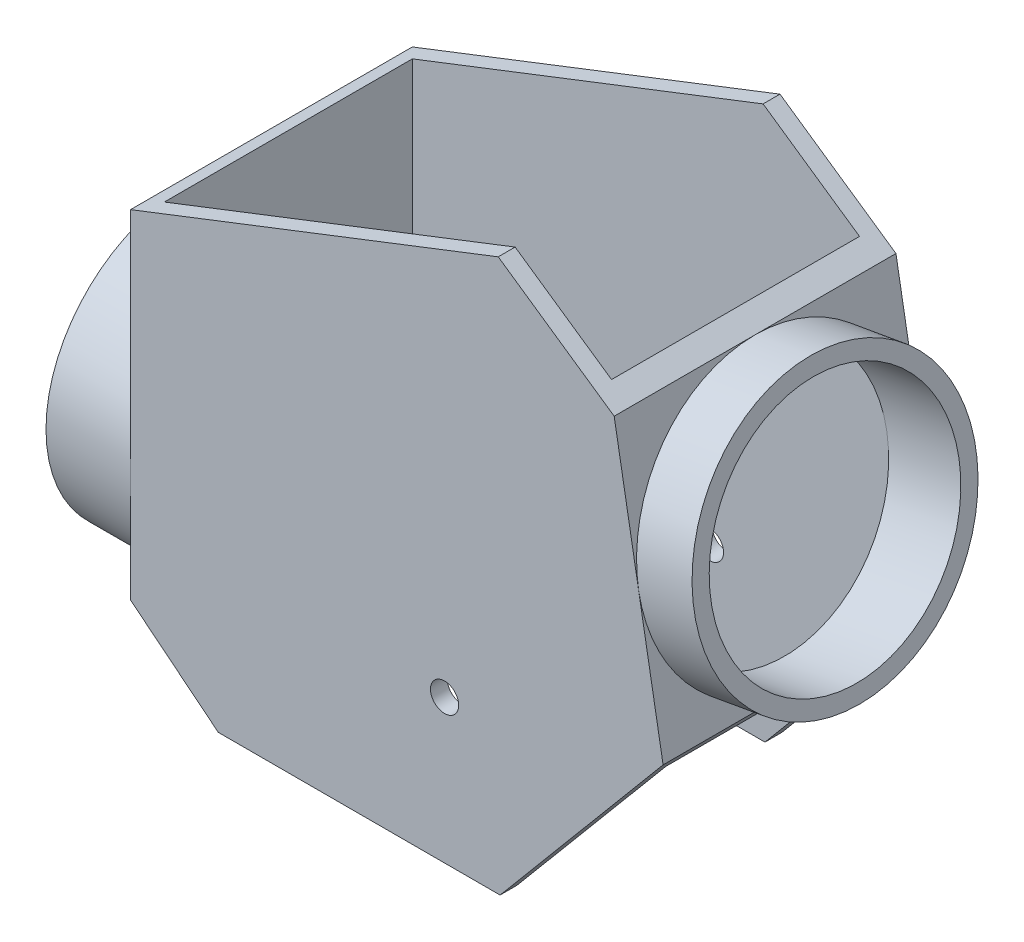
SolidWorks part; units mm, degrees
ref_plane "Plan de face" through (0, 0, 0) normal (0, 0, 1) x (1, 0, 0)
ref_plane "Plan de dessus" through (0, 0, 0) normal (0, 1, 0) x (1, 0, 0)
ref_plane "Plan de droite" through (0, 0, 0) normal (1, 0, 0) x (0, 0, -1)
sketch "Esquisse1" plane through (0, 0, 0) normal (0, 0, 1) x (1, 0, 0)
  line L0 (-31.8099, -22.4289) -> (-16.2349, -34.9756)
  line L1 (33.7651, -34.9756) -> (-16.2349, -34.9756)
  line L2 (33.7651, -34.9756) -> (62.6905, -0.5036)
  line L3 (62.6905, -0.5036) -> (54.0081, 48.7368)
  line L4 (54.0081, 48.7368) -> (33.4325, 62.937)
  line L5 (33.4325, 62.937) -> (-31.8099, 37.5711)
  line L6 (-31.8099, 37.5711) -> (-31.8099, -22.4289)
  dimension "D1" = 50
  dimension "D2" = 60
  dimension "D3" = 50
  dimension "D4" = 70
  dimension "D5" = 25
  dimension "D6" = 45
  dimension "D7" = 20
  dimension "D8" = 230
  dimension "D9" = 280
extrude "Boss.-Extru.1" add sketch "Esquisse1" along normal blind 50
sketch "Esquisse3" plane through (60.714, 10.7055, 0) normal (0.9848, 0.1736, 0) x (0, 0, -1)
  circle A1 centre (-25, 13.618) radius 25
extrude "Boss.-Extru.2" add sketch "Esquisse3" along normal blind 10
sketch "Esquisse4" plane through (-31.8099, 0, 0) normal (-1, 0, 0) x (0, 0, 1)
  line L0 (0, -28.7022) -> (50, -28.7022) construction
  line L1 (0, -22.4289) -> (0, -34.9756) construction
  line L2 (50, -22.4289) -> (50, -34.9756) construction
  circle A1 centre (25, -3.7022) radius 25
extrude "Boss.-Extru.3" add sketch "Esquisse4" along normal mid plane 30
shell "Coque2" thickness 3 removed face at (-46.8099, -3.7022, 50) removed face at (45.7779, 54.4169, 25) removed face at (0.8113, 50.2541, 25) removed face at (63.8562, 50.4733, 25) removed face at (51.1203, -14.2924, 25) removed face at (8.7651, -34.9756, 25)
sketch "Esquisse6" plane through (0, 0, 50) normal (0, 0, 1) x (1, 0, 0)
  line L0 (-31.8099, -22.4289) -> (62.6905, -0.5036) construction
  line L1 (33.7651, -34.9756) -> (0.8113, 50.2541) construction
  line L2 (33.4325, 62.937) -> (-31.8099, 37.5711) construction
  circle A0 centre (23.915, -9.5) radius 2.5
  point P9 (23.915, -9.5)
  dimension "D1" = 5
extrude "Enlèv. mat.-Extru.1" cut sketch "Esquisse6" against normal through all
